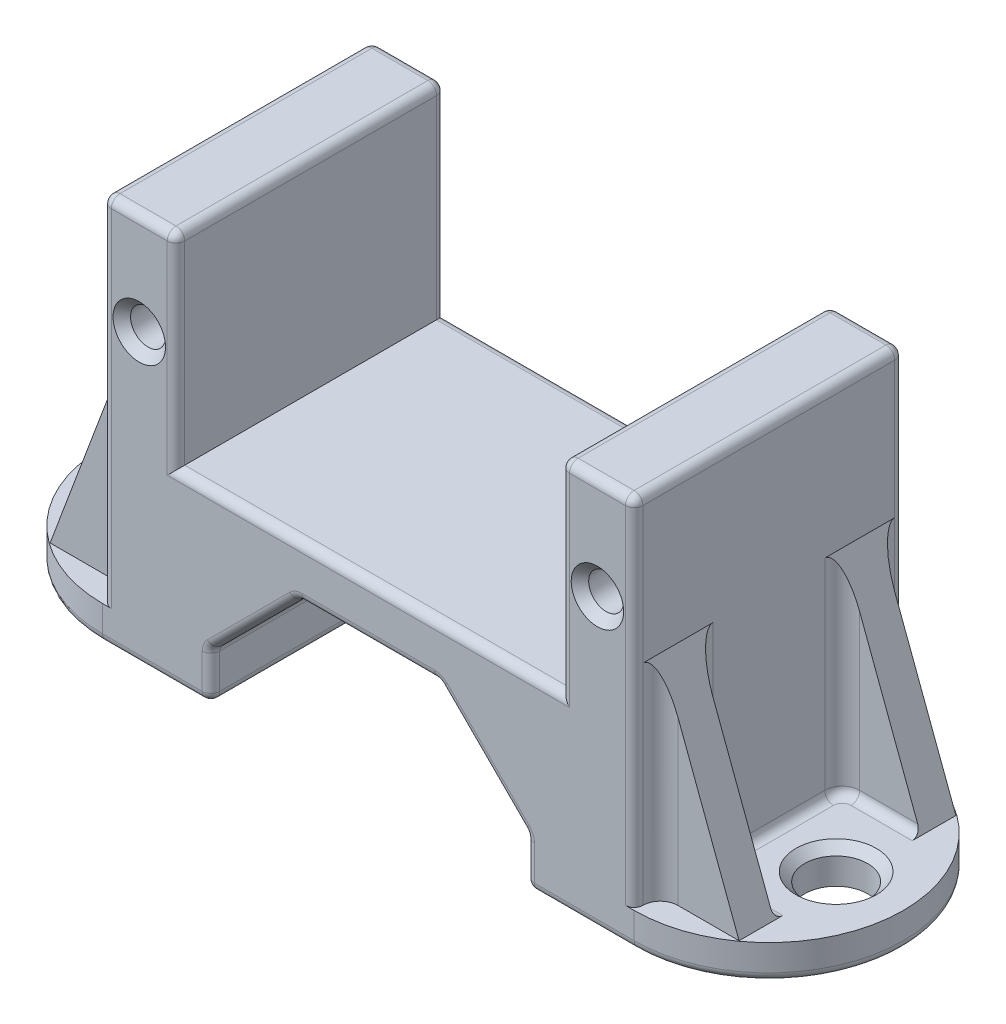
SolidWorks part; units mm, degrees
ref_plane "Plano frontal" through (0, 0, 0) normal (0, 0, 1) x (1, 0, 0)
ref_plane "Plano superior" through (0, 0, 0) normal (0, 1, 0) x (1, 0, 0)
ref_plane "Plano direito" through (0, 0, 0) normal (1, 0, 0) x (0, 0, -1)
sketch "Sketch1" plane through (0, 0, 0) normal (0, 1, 0) x (1, 0, 0)
  line L1 (-11, 7.7) -> (11, 7.7)
  line L2 (-11, 7.7) -> (-11, -7.7)
  line L3 (-11, -7.7) -> (11, -7.7)
  line L4 (11, 7.7) -> (11, -7.7)
  point P4 (0, 7.7)
  point P6 (-11, 0)
  dimension "D1" = 22
  dimension "D2" = 15.4
extrude "Boss-Extrude1" add sketch "Sketch1" along normal mid plane 10.7
sketch "Sketch3" plane through (0, -5.35, 0) normal (0, -1, 0) x (1, 0, 0)
  line L0 (-9, 5.7) -> (-9, -5.7)
  line L1 (-9, -5.7) -> (9, -5.7)
  line L2 (9, -5.7) -> (9, 5.7)
  line L3 (9, 5.7) -> (-9, 5.7)
  line L4 (-11, 7.7) -> (-11, -7.7)
  line L5 (-11, -7.7) -> (11, -7.7)
  line L6 (11, -7.7) -> (11, 7.7)
  line L7 (11, 7.7) -> (-11, 7.7)
  line L8 (-11, 7.7) -> (-11, -7.7) construction
  line L9 (-11, -7.7) -> (11, -7.7) construction
  line L10 (11, -7.7) -> (11, 7.7) construction
  line L11 (11, 7.7) -> (-11, 7.7) construction
  dimension "D1" = 0
  dimension "D2" = 2
extrude "Cut-Extrude2" cut sketch "Sketch3" against normal offset from surface (7.7 mm away) 3 up to face at (0, 5.35, 0)
sketch "Sketch8" plane through (0, 0, 0) normal (0, 0, 1) x (1, 0, 0)
  line L1 (-9, 2.35) -> (9, 2.35)
  line L2 (-9, 2.35) -> (-9, -5.35)
  line L3 (-9, -5.35) -> (9, -5.35)
  line L4 (9, 2.35) -> (9, -5.35)
extrude "Cut-Extrude3" cut sketch "Sketch8" against normal through all both and the other way through all
sketch "Sketch2" plane through (-11, 0, 0) normal (-1, 0, 0) x (0, 0, 1)
  line L0 (7.7, 5.35) -> (7.7, -5.35) construction
  line L1 (-7.7, -5.35) -> (7.7, -5.35)
  line L2 (-7.7, -5.35) -> (-7.7, 16.95)
  line L3 (-7.7, 16.95) -> (7.7, 16.95)
  line L4 (7.7, -5.35) -> (7.7, 16.95)
  dimension "D1" = 22.3
extrude "Boss-Extrude2" add sketch "Sketch2" along normal blind 4.2
mirror "Mirror1" about plane through (0, 0, 0) normal (1, 0, 0) of "Boss-Extrude2"
sketch "Sketch4" plane through (0, -5.35, 0) normal (0, -1, 0) x (1, 0, 0)
  line L1 (-15.2, -7.7) -> (-11, -7.7) construction
  line L2 (-15.2, -7.7) -> (-15.2, 7.7)
  line L3 (-22.9, 0) -> (-15.2, 0) construction
  arc A0 (-15.2, 7.7) -> (-15.2, -7.7) centre (-15.2, 0) ccw
  circle A1 centre (-19.05, 0) radius 1.5 construction
  circle A2 centre (-19.05, 0) radius 1.8
  dimension "D1" = 3
  dimension "D3" = 2.05
  dimension "D2" = 0.3
extrude "Boss-Extrude4" add sketch "Sketch4" against normal blind 2
ref_plane "Plane1" through (0, 0, 5.2) normal (0, 0, 1) x (1, 0, 0)
sketch "Sketch7" plane through (0, 0, 5.2) normal (0, 0, 1) x (1, 0, 0)
  line L0 (-19.7, -3.35) -> (-15.2, 8.65)
  line L1 (-15.2, -3.35) -> (-22.9, -3.35) construction
  line L2 (-15.2, -3.35) -> (-15.2, 16.95) construction
  dimension "D1" = 4.5
  dimension "D2" = 12
rib "Rib9" sketch "Sketch7" sketch "Sketch7" thickness 2 extrusion direction parallel to sketch draft on no parameters "D1"=2
mirror "Mirror3" about plane through (0, 0, 0) normal (0, 0, 1) of "Rib9"
mirror "Mirror4" about plane through (0, 0, 0) normal (1, 0, 0) of "Mirror3", "Rib9", "Boss-Extrude4"
chamfer "Chamfer1" distance 5 angle 45 2 edges at (-9, 2.35, 0) (9, 2.35, 0)
fillet "Fillet2" radius 1 8 edges at (-15.2, 2.65, 4.2) (-15.2, 2.65, -4.2) (-15.2, 2.65, 6.2) (-15.2, 2.65, -6.2) (15.2, 2.65, -6.2) (15.2, 2.65, -4.2) (15.2, 2.65, 4.2) (15.2, 2.65, 6.2)
fillet "Fillet5" radius 0.5 50 edges at (-22.9, -5.35, 0) (-17.95, -3.35, -4.2) (-15.4929, -3.35, -3.9071) (-17.95, -3.35, 4.2) (-15.4929, -3.35, 3.9071) (17.95, -3.35, -4.2) (15.4929, -3.35, -3.9071) (17.95, -3.35, 4.2) (15.4929, -3.35, 3.9071) (-9, -5.35, 0) (-9, -2.65, 0) (9, -5.35, 0) (9, -2.65, 0) (4, 2.35, 0) (-4, 2.35, 0) (22.9, -5.35, 0) (12.1, -5.35, -7.7) (15.2, 6.8, -7.7) (13.1, 16.95, -7.7) (11, 11.15, -7.7) (0, 5.35, -7.7) (-11, 11.15, -7.7) (-15.2, 6.8, -7.7) (-12.1, -5.35, -7.7) (-9, -4, -7.7) (-6.5, -0.15, -7.7) (0, 2.35, -7.7) (6.5, -0.15, -7.7) (9, -4, -7.7) (-15.2, 6.8, 7.7) (-11, 11.15, 7.7) (0, 5.35, 7.7) (11, 11.15, 7.7) (13.1, 16.95, 7.7) (15.2, 6.8, 7.7) (12.1, -5.35, 7.7) (9, -4, 7.7) (6.5, -0.15, 7.7) (0, 2.35, 7.7) (-6.5, -0.15, 7.7) (-9, -4, 7.7) (-12.1, -5.35, 7.7) (-11, 16.95, 0) (-13.1, 16.95, 7.7) (-15.2, 16.95, 0) (-13.1, 16.95, -7.7) (-15.2, -3.35, 0) (15.2, -3.35, 0) (15.2, 16.95, 0) (11, 16.95, 0)
sketch "Sketch10" plane through (0, 0, 0) normal (0, 0, 1) x (1, 0, 0)
  line L0 (-13.1, 16.95) -> (-13.1, 5.35) construction
  line L1 (-14.7, 16.95) -> (-11.5, 16.95) construction
  line L3 (-11, 5.35) -> (-13.1, 5.35) construction
  line L4 (0, -8.47) -> (0, 8.47) construction
  circle A0 centre (-13.1, 11.15) radius 1
  circle A1 centre (13.1, 11.15) radius 1
  dimension "D1" = 2
extrude "Cut-Extrude5" cut sketch "Sketch10" against normal through all both and the other way through all
chamfer "Chamfer4" distance 0.5 angle 45 6 edges at (19.05, -3.35, -1.8) (-19.05, -3.35, -1.8) (-12.1, 11.15, -7.7) (-12.1, 11.15, 7.7) (12.1, 11.15, 7.7) (12.1, 11.15, -7.7)
